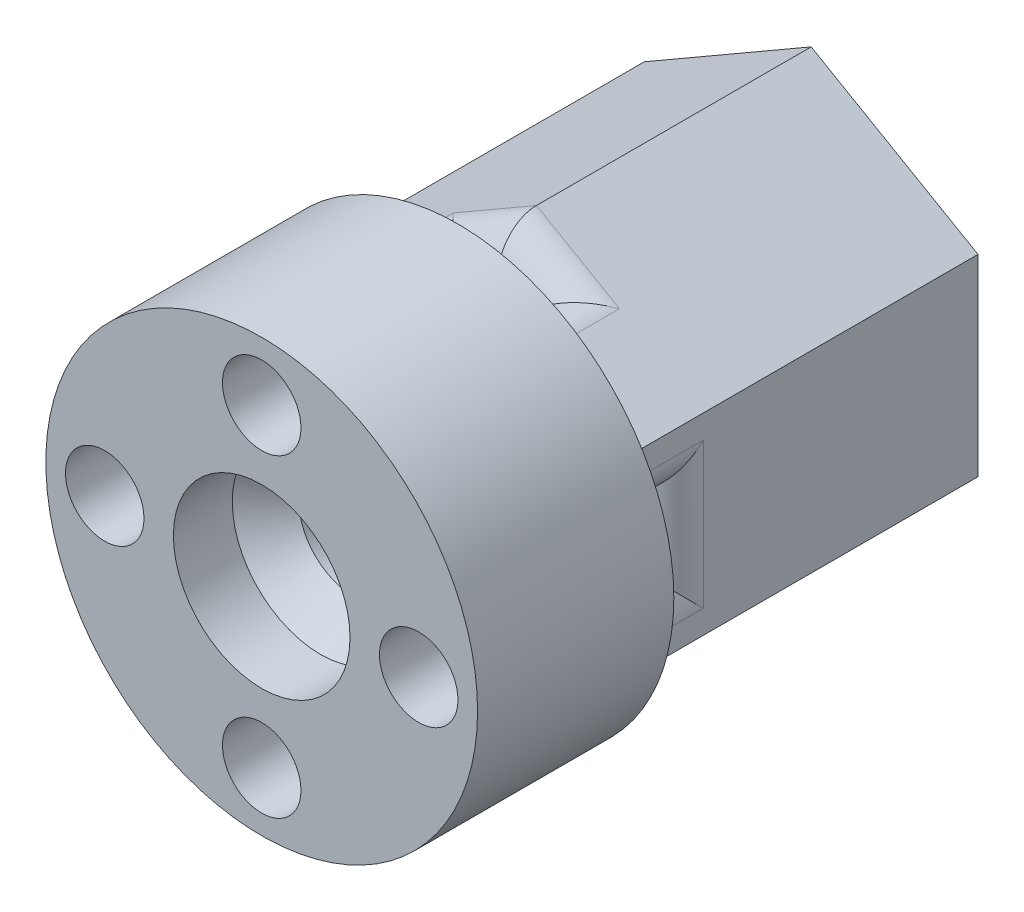
SolidWorks part; units mm, degrees
ref_plane "Plan de face" through (0, 0, 0) normal (1, 0, 0) x (0, 1, 0)
ref_plane "Plan de dessus" through (0, 0, 0) normal (0, 0, 1) x (0, 1, 0)
ref_plane "Plan de droite" through (0, 0, 0) normal (0, 1, 0) x (-1, 0, 0)
sketch "Esquisse1" plane through (0, 0, 0) normal (0, 0, 1) x (0, 1, 0)
  line L1 (9.815, 0) -> (4.9075, 8.5)
  line L2 (4.9075, 8.5) -> (-4.9075, 8.5)
  line L3 (-4.9075, 8.5) -> (-9.815, 0)
  line L4 (-9.815, 0) -> (-4.9075, -8.5)
  line L5 (-4.9075, -8.5) -> (4.9075, -8.5)
  line L6 (4.9075, -8.5) -> (9.815, 0)
  circle A0 centre (0, 0) radius 8.5 construction
  circle A1 centre (0, 0) radius 6
  dimension "D1" = 17
  dimension "D2" = 12
extrude "Boss.-Extru.1" add sketch "Esquisse1" along normal blind 15
thread "Filetage1" pitch 1.5 method cut profile "Profil de filetage1" start angle 0, offset 0, length 0, pitch 1.5, diameter 12
ref_plane "Plan1" through (-6, 0, 15) normal (0, -1, 0) x (-1, 0, 0)
sketch "Profil de filetage1" plane through (-6, 0, 15) normal (0, -1, 0) x (-1, 0, 0)
  line L0 (0, 0) -> (0, 1.5) construction
  line L1 (0, 0) -> (0.8119, 0.4687)
  line L2 (0.8119, 0.4687) -> (0.8119, 0.6562)
  line L3 (0.8119, 0.6562) -> (0, 1.125)
  line L4 (0.8119, 0.5625) -> (0, 0.5625) construction
  line L11 (0, 0) -> (0, 1.125)
  point P2 (0, 0)
  dimension "Pitch" = 1.5
  dimension "Profile_Angle" = 60
  dimension "Profile_Land" = 0.1875
  dimension "Profile_Height" = 0.8119
sketch "Esquisse5" plane through (0, 0, 15) normal (0, 0, 1) x (1, 0, 0)
  line L1 (8.5, -4.9075) -> (8.5, 4.9075)
  line L2 (8.5, 4.9075) -> (0, 9.815)
  line L3 (0, 9.815) -> (-8.5, 4.9075)
  line L4 (-8.5, 4.9075) -> (-8.5, -4.9075)
  line L5 (-8.5, -4.9075) -> (0, -9.815)
  line L6 (0, -9.815) -> (8.5, -4.9075)
  circle A0 centre (0, 0) radius 8.5 construction
extrude "Boss.-Extru.2" add sketch "Esquisse5" along normal blind 2
sketch "Esquisse8" plane through (0, 0, 17) normal (0, 0, 1) x (1, 0, 0)
  line L1 (8.5, 4.9075) -> (0, 9.815)
  line L2 (0, 9.815) -> (-8.5, 4.9075)
  line L3 (-8.5, 4.9075) -> (-8.5, -4.9075)
  line L4 (-8.5, -4.9075) -> (0, -9.815)
  line L5 (0, -9.815) -> (8.5, -4.9075)
  line L6 (8.5, -4.9075) -> (8.5, 4.9075)
  circle A1 centre (0, 0) radius 8.5 construction
extrude "Boss.-Extru.3" add sketch "Esquisse8" along normal blind 11
sketch "Esquisse9" plane through (0, 0, 28) normal (0, 0, 1) x (1, 0, 0)
  circle A0 centre (0, 0) radius 6 construction
  circle A1 centre (0, 0) radius 8.34
  point P0 (0, 0)
  dimension "D1" = 12
  dimension "D2" = 16.68
hole_wizard "Fraisage pour vis à tête fraisée M61" positions "Esquisse9" profile "Esquisse10" countersink size "M6" standard "ISO" end condition through all
sketch "Esquisse10" plane through (0, 0, 28) normal (1, 0, 0) x (0, -1, 0)
  line L0 (0, 0) -> (0, 28.5553)
  line L1 (0, 28.5553) -> (2.8, 28.5553)
  line L2 (2.8, 28.5553) -> (2.8, 4.7)
  line L3 (2.8, 4.7) -> (4.5, 3)
  line L4 (4.5, 3) -> (4.5, 0)
  line L6 (4.5, 0) -> (0, 0)
  line L7 (-2.8, 4.7) -> (-4.5, 3) construction
  line L11 (0, -6.35) -> (0, 107.95) construction
  dimension "Diamètre du perçage jusqu'au prochain" = 5.6
  dimension "Profondeur du perçage jusqu'au prochain" = 28.5553
  dimension "Diamètre du fraisage" = 9
  dimension "Angle du fraisage" = 90
  dimension "Dégagement de la tête" = 3
sketch "Esquisse11" plane through (0, 0, 28) normal (0, 0, 1) x (1, 0, 0)
  circle A0 centre (0, 0) radius 4.5
  circle A1 centre (0, 0) radius 11
  dimension "D1" = 22
extrude "Boss.-Extru.4" add sketch "Esquisse11" against normal blind 10
sketch "Esquisse12" plane through (0, 0, 28) normal (0, 0, 1) x (1, 0, 0)
  line L0 (0, 0) -> (0, -12.5133) construction
  line L1 (0, -12.5133) -> (0, 12.18) construction
  line L2 (0, 12.18) -> (0, 0) construction
  line L3 (0, 0) -> (18.0276, 0) construction
  line L4 (18.0276, 0) -> (-15.0584, 0) construction
  circle A0 centre (8, 0) radius 2
  circle A1 centre (0, -8) radius 2
  circle A2 centre (-8, 0) radius 2
  circle A3 centre (0, 8) radius 2
  point P18 (0, 0)
  dimension "D1" = 4
  dimension "D2" = 8
  dimension "D3" = 4
extrude "Enlèv. mat.-Extru.1" cut sketch "Esquisse12" against normal blind 12
fillet "Congé1" radius 2 14 edges at (-8.5, 1.9365, 17) (-8.5, -1.9365, 17) (-8.5, 0, 16) (1.8569, 8.7429, 17) (-1.8569, 8.7429, 17) (-0.9285, 9.2789, 16) (0.9285, 9.2789, 16) (8.5, 1.9365, 17) (8.5, -1.9365, 17) (8.5, 0, 16) (1.8569, -8.7429, 17) (-1.8569, -8.7429, 17) (0.9285, -9.2789, 16) (-0.9285, -9.2789, 16)
